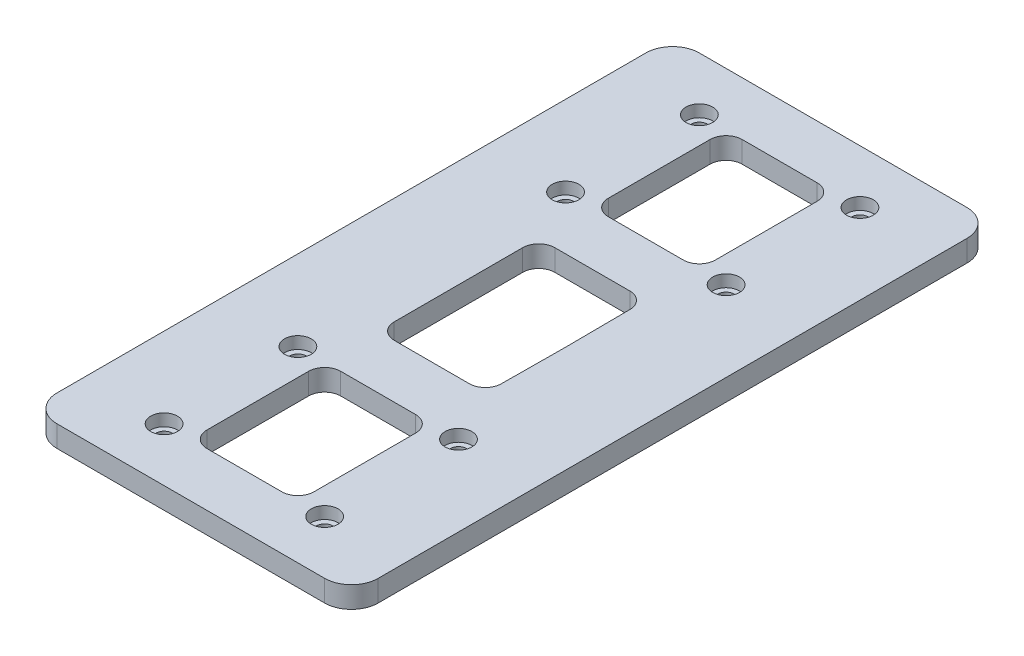
SolidWorks part; units mm, degrees
ref_plane "前视基准面" through (0, 0, 0) normal (0, 0, 1) x (1, 0, 0)
ref_plane "上视基准面" through (0, 0, 0) normal (0, 1, 0) x (1, 0, 0)
ref_plane "右视基准面" through (0, 0, 0) normal (1, 0, 0) x (0, 0, -1)
sketch "草图1" plane through (0, 0, 0) normal (0, 1, 0) x (1, 0, 0)
  line L78 (-262.5275, 71.1197) -> (-135.5176, 71.1197) construction
  line L110 (-206.8401, 96.1197) -> (-192.8401, 96.1197)
  line L111 (-209.8401, 99.1197) -> (-209.8401, 118.1197)
  line L112 (-206.8401, 121.1197) -> (-192.8401, 121.1197)
  line L113 (-189.8401, 99.1197) -> (-189.8401, 118.1197)
  line L117 (-199.8401, 146.5986) -> (-199.8401, 7.3826) construction
  line L118 (-199.8401, 131.1197) -> (-224.8401, 131.1197)
  line L119 (-199.8401, 131.1197) -> (-174.8401, 131.1197)
  line L120 (-229.8401, 126.1197) -> (-229.8401, 16.1197)
  line L121 (-169.8401, 126.1197) -> (-169.8401, 16.1197)
  line L122 (-199.8401, 11.1197) -> (-174.8401, 11.1197)
  line L123 (-199.8401, 11.1197) -> (-224.8401, 11.1197)
  line L124 (-189.8401, 43.1197) -> (-189.8401, 24.1197)
  line L125 (-206.8401, 21.1197) -> (-192.8401, 21.1197)
  line L126 (-209.8401, 43.1197) -> (-209.8401, 24.1197)
  line L127 (-206.8401, 46.1197) -> (-192.8401, 46.1197)
  line L128 (-209.8401, 59.1197) -> (-209.8401, 83.1197)
  line L129 (-192.8181, 86.1197) -> (-206.8401, 86.1197)
  line L130 (-189.8181, 83.1418) -> (-189.7296, 71.1197)
  line L131 (-189.8181, 59.0976) -> (-189.7296, 71.1197)
  line L132 (-192.8181, 56.1197) -> (-206.8401, 56.1197)
  circle A0 centre (-214.8401, 121.1197) radius 1.5
  circle A6 centre (-214.8401, 96.1197) radius 1.5
  circle A65 centre (-184.8401, 121.1197) radius 1.5
  circle A66 centre (-184.8401, 96.1197) radius 1.5
  circle A93 centre (-214.8401, 96.1197) radius 2.5
  circle A94 centre (-184.8401, 96.1197) radius 2.5
  circle A95 centre (-184.8401, 121.1197) radius 2.5
  circle A96 centre (-214.8401, 121.1197) radius 2.5
  arc A117 (-206.8401, 96.1197) -> (-209.8401, 99.1197) centre (-206.8401, 99.1197) cw
  arc A118 (-192.8401, 96.1197) -> (-189.8401, 99.1197) centre (-192.8401, 99.1197) ccw
  arc A119 (-192.8401, 121.1197) -> (-189.8401, 118.1197) centre (-192.8401, 118.1197) cw
  arc A120 (-209.8401, 118.1197) -> (-206.8401, 121.1197) centre (-206.8401, 118.1197) cw
  arc A137 (-169.8401, 126.1197) -> (-174.8401, 131.1197) centre (-174.8401, 126.1197) ccw
  arc A138 (-229.8401, 126.1197) -> (-224.8401, 131.1197) centre (-224.8401, 126.1197) cw
  arc A139 (-229.8401, 16.1197) -> (-224.8401, 11.1197) centre (-224.8401, 16.1197) ccw
  arc A140 (-169.8401, 16.1197) -> (-174.8401, 11.1197) centre (-174.8401, 16.1197) cw
  arc A141 (-209.8401, 24.1197) -> (-206.8401, 21.1197) centre (-206.8401, 24.1197) ccw
  arc A142 (-192.8401, 21.1197) -> (-189.8401, 24.1197) centre (-192.8401, 24.1197) ccw
  arc A143 (-192.8401, 46.1197) -> (-189.8401, 43.1197) centre (-192.8401, 43.1197) cw
  arc A144 (-206.8401, 46.1197) -> (-209.8401, 43.1197) centre (-206.8401, 43.1197) ccw
  circle A145 centre (-214.8401, 21.1197) radius 2.5
  circle A146 centre (-184.8401, 21.1197) radius 2.5
  circle A147 centre (-184.8401, 46.1197) radius 2.5
  circle A148 centre (-214.8401, 46.1197) radius 2.5
  circle A149 centre (-184.8401, 46.1197) radius 1.5
  circle A150 centre (-184.8401, 21.1197) radius 1.5
  circle A151 centre (-214.8401, 46.1197) radius 1.5
  circle A152 centre (-214.8401, 21.1197) radius 1.5
  arc A153 (-189.8181, 83.1418) -> (-192.8181, 86.1197) centre (-192.8181, 83.1197) ccw
  arc A154 (-206.8401, 86.1197) -> (-209.8401, 83.1197) centre (-206.8401, 83.1197) ccw
  arc A155 (-189.8181, 59.0976) -> (-192.8181, 56.1197) centre (-192.8181, 59.1197) cw
  arc A156 (-206.8401, 56.1197) -> (-209.8401, 59.1197) centre (-206.8401, 59.1197) cw
  point P29 (-199.8401, 108.6197)
  point P32 (-189.7296, 71.1197)
  point P37 (-166.8323, -26.0766)
  point P47 (-169.8401, 71.1197)
  point P51 (-229.8401, 71.1197)
  point P65 (-209.8401, 71.1197)
  point P84 (-199.8401, 33.6197)
  dimension "D4" = 3
  dimension "D6" = 3
  dimension "D2" = 25
  dimension "D1" = 5
  dimension "D3" = 30
extrude "凸台-拉伸1" add sketch "草图1" along normal blind 4 contours A140 L121 A137 L119 L118 A138 L120 A139 L123 L122 A147 A145 A144 L127 A143 L124 A142 L125 A141 L126 A96 A95 A94 A93 L111 A120 L112 A119 L113 A118 L110 A117 A146 A148 L132 A156 L128 A154 L129 A153 region at (-187.3401, 0, -129.7781)
extrude "凸台-拉伸2" add sketch "草图1<32>" along normal blind 1.75 contours A93 A6 | A94 A66 | A95 A65 | A96 A0 region at (-217.2694, 0, -96.1197) region at (-187.2694, 0, -96.1197) region at (-187.2694, 0, -121.1197) region at (-217.2694, 0, -121.1197)
sketch "草图1<32>" plane through (0, 0, 0) normal (0, 1, 0) x (1, 0, 0) same geometry as "草图1"
extrude "凸台-拉伸3" add sketch "草图1<33>" along normal blind 1.75 contours A148 A151 | A147 A149 | A145 A152 | A146 A150 region at (-217.2694, 0, -21.1197) region at (-187.2694, 0, -21.1197) region at (-187.2694, 0, -46.1197) region at (-217.2694, 0, -46.1197)
sketch "草图1<33>" plane through (0, 0, 0) normal (0, 1, 0) x (1, 0, 0) same geometry as "草图1"
